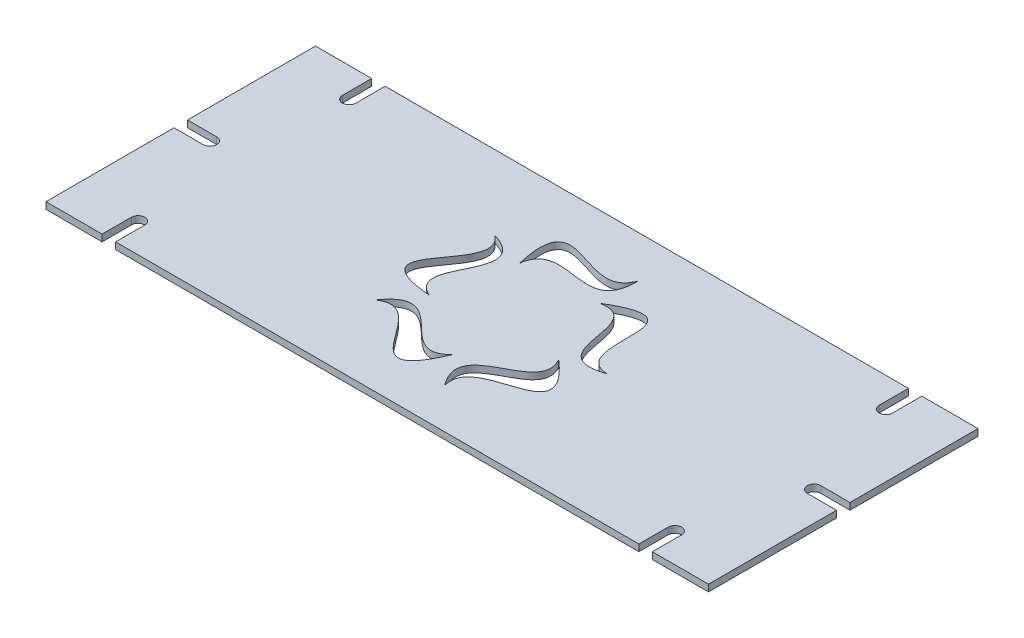
SolidWorks part; units mm, degrees
ref_plane "Front Plane" through (0, 0, 0) normal (0, 0, 1) x (1, 0, 0)
ref_plane "Top Plane" through (0, 0, 0) normal (0, 1, 0) x (1, 0, 0)
ref_plane "Right Plane" through (0, 0, 0) normal (1, 0, 0) x (0, 0, -1)
sketch "Sketch1" plane through (0, 0, 0) normal (0, 1, 0) x (1, 0, 0)
  line L1 (-147.5, -60) -> (147.5, -60)
  line L2 (-147.5, -60) -> (-147.5, 60)
  line L3 (-147.5, 60) -> (147.5, 60)
  line L4 (147.5, -60) -> (147.5, 60)
  line L5 (-147.5, -60) -> (147.5, 60) construction
  line L6 (-147.5, 60) -> (147.5, -60) construction
  point P0 (0, 0)
  dimension "D1" = 295
  dimension "D2" = 120
extrude "Boss-Extrude1" add sketch "Sketch1" along normal blind 3
sketch "Sketch2" plane through (0, 3, 0) normal (0, 1, 0) x (1, 0, 0)
  line L0 (0, -60) -> (0, 60) construction
  line L1 (147.5, 60) -> (-147.5, 60) construction
  line L2 (0, 60) -> (0, -60) construction
  line L3 (-147.5, 0) -> (147.5, 0) construction
  line L4 (147.5, -60) -> (147.5, 60) construction
  line L5 (-122.5, 60) -> (-122.5, 47)
  line L6 (-116.5, 47) -> (-116.5, 60)
  line L7 (-116.5, 60) -> (-122.5, 60)
  line L8 (-147.5, 60) -> (-147.5, -60) construction
  line L9 (116.5, 60) -> (122.5, 60)
  line L10 (116.5, 47) -> (116.5, 60)
  line L11 (122.5, 60) -> (122.5, 47)
  line L12 (122.5, -60) -> (122.5, -47)
  line L13 (116.5, -47) -> (116.5, -60)
  line L14 (116.5, -60) -> (122.5, -60)
  line L15 (-116.5, -60) -> (-122.5, -60)
  line L16 (-116.5, -47) -> (-116.5, -60)
  line L17 (-122.5, -60) -> (-122.5, -47)
  line L18 (147.5, 3) -> (134.5, 3)
  line L19 (134.5, -3) -> (147.5, -3)
  line L20 (147.5, -3) -> (147.5, 3)
  line L21 (-147.5, -3) -> (-147.5, 3)
  line L22 (-134.5, -3) -> (-147.5, -3)
  line L23 (-147.5, 3) -> (-134.5, 3)
  arc A0 (-122.5, 47) -> (-116.5, 47) centre (-119.5, 47) ccw
  arc A1 (122.5, 47) -> (116.5, 47) centre (119.5, 47) cw
  arc A2 (122.5, -47) -> (116.5, -47) centre (119.5, -47) ccw
  arc A3 (-122.5, -47) -> (-116.5, -47) centre (-119.5, -47) cw
  arc A4 (134.5, 3) -> (134.5, -3) centre (134.5, 0) ccw
  arc A5 (-134.5, 3) -> (-134.5, -3) centre (-134.5, 0) cw
  point P35 (0, 0)
  point P43 (0, 0)
  dimension "D5" = 3
  dimension "D1" = 6
  dimension "D2" = 13
  dimension "D3" = 25
  dimension "D4" = 13
extrude "Cut-Extrude1" cut sketch "Sketch2" against normal blind 10
sketch "Sketch3" plane through (0, 3, 0) normal (0, 1, 0) x (1, 0, 0)
  circle A0 centre (0, 0) radius 45 construction
  spline S0 degree 3 poles (14.9599, 24.1191) (49.5863, 45.0005) (22.7612, -0.9075) (43.84, -1.4361) knots 0 0 0 0 1 1 1 1
  spline S1 degree 3 poles (43.84, -1.4361) (18.455, -10.3122) (35.0535, 27.9627) (14.9599, 24.1191) knots 0 0 0 0 1 1 1 1
  spline S2 degree 3 poles (12.1815, -42.1381) (-4.1046, -20.7384) (37.4263, -24.6969) (27.5615, -6.7745) knots 0 0 0 0 1 1 1 1
  spline S3 degree 3 poles (27.5615, -6.7745) (58.121, -33.2535) (6.1705, -21.9276) (12.1815, -42.1381) knots 0 0 0 0 1 1 1 1
  spline S4 degree 3 poles (-36.3114, -24.6067) (-20.9918, -2.5049) (-11.9228, -43.2262) (2.0741, -28.3059) knots 0 0 0 0 1 1 1 1
  spline S5 degree 3 poles (2.0741, -28.3059) (-13.6655, -65.5523) (-18.9476, -12.6445) (-36.3114, -24.6067) knots 0 0 0 0 1 1 1 1
  spline S6 degree 3 poles (-34.6232, 26.9303) (-8.8691, 19.1903) (-44.7949, -2.0184) (-26.2796, -10.7196) knots 0 0 0 0 1 1 1 1
  spline S7 degree 3 poles (-26.2796, -10.7196) (-66.5668, -7.2601) (-17.8808, 14.1129) (-34.6232, 26.9303) knots 0 0 0 0 1 1 1 1
  spline S8 degree 3 poles (14.9131, 41.2505) (15.5104, 14.3651) (-15.762, 41.9788) (-18.3158, 21.6809) knots 0 0 0 0 1 1 1 1
  spline S9 degree 3 poles (-18.3158, 21.6809) (-27.475, 61.0653) (7.8967, 21.3668) (14.9131, 41.2505) knots 0 0 0 0 1 1 1 1
  point P35 (0, 0)
  dimension "D1" = 90
extrude "Cut-Extrude3" cut sketch "Sketch3" against normal blind 10
